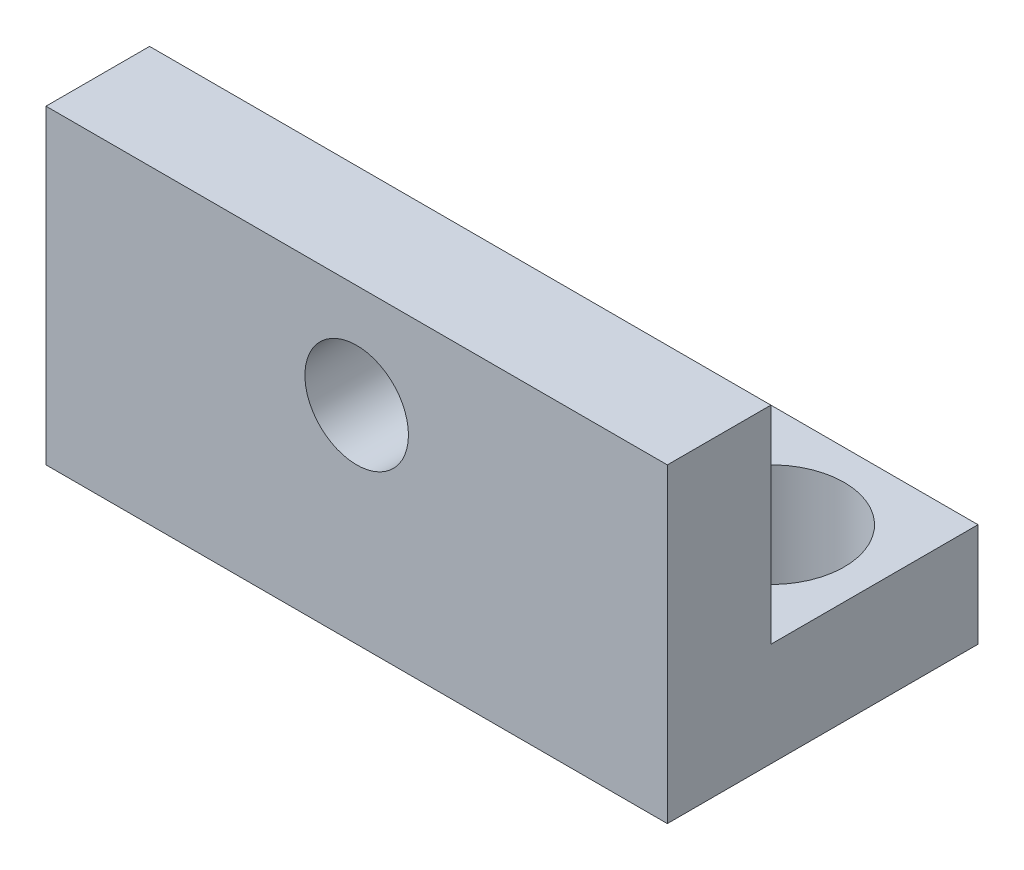
SolidWorks part; units mm, degrees
material "ABS"
ref_plane "Front Plane" through (0, 0, 0) normal (0, 0, 1) x (1, 0, 0)
ref_plane "Top Plane" through (0, 0, 0) normal (0, 1, 0) x (1, 0, 0)
ref_plane "Right Plane" through (0, 0, 0) normal (1, 0, 0) x (0, 0, -1)
sketch "Sketch1" plane through (0, 0, 0) normal (0, 0, 1) x (1, 0, 0)
  line L1 (-9.525, -3.175) -> (9.525, -3.175)
  line L2 (-9.525, -3.175) -> (-9.525, 3.175)
  line L3 (-9.525, 3.175) -> (9.525, 3.175)
  line L4 (9.525, -3.175) -> (9.525, 3.175)
  line L5 (-9.525, -3.175) -> (9.525, 3.175) construction
  line L6 (-9.525, 3.175) -> (9.525, -3.175) construction
  circle A0 centre (0, 0) radius 1.5875
  point P0 (0, 0)
  dimension "D3" = 3.175
  dimension "D1" = 6.35
  dimension "D2" = 19.05
extrude "Boss-Extrude1" add sketch "Sketch1" along normal blind 3.175
sketch "Sketch2" plane through (0, -3.175, 0) normal (0, -1, 0) x (1, 0, 0)
  line L0 (-9.525, 3.175) -> (9.525, 3.175) construction
  line L1 (-9.525, 3.175) -> (9.525, 3.175)
  line L2 (-9.525, 3.175) -> (-9.525, -6.35)
  line L3 (-9.525, -6.35) -> (9.525, -6.35)
  line L4 (9.525, 3.175) -> (9.525, -6.35)
  line L5 (-9.525, 3.175) -> (-9.525, 0) construction
  line L7 (3.4925, 0) -> (-3.4925, 0) construction
  dimension "D1" = 6.35
extrude "Boss-Extrude2" add sketch "Sketch2" along normal blind 3.175
hole_wizard "#8 Clearance Hole1" positions "Sketch3" profile "Sketch4" hole size "#8" standard "ANSI Inch" end condition through all
sketch "Sketch3" plane through (0, -6.35, 0) normal (0, -1, 0) x (-1, 0, 0)
  line L0 (9.525, 3.175) -> (-9.525, 3.175) construction
  line L1 (9.525, 0) -> (9.525, 6.35) construction
  line L2 (-9.525, 6.35) -> (-9.525, 0) construction
  line L4 (0, 6.35) -> (0, -3.175) construction
  line L5 (9.525, 6.35) -> (-9.525, 6.35) construction
  line L6 (-9.525, -3.175) -> (9.525, -3.175) construction
  line L8 (-9.525, 6.35) -> (-9.525, -3.175) construction
  point P9 (6.35, 3.175)
  point P11 (-6.35, 3.175)
  dimension "D1" = 3.175
sketch "Sketch4" plane through (6.35, -6.35, -3.175) normal (1, 0, 0) x (0, 0, -1)
  line L0 (0, 0) -> (0, 9.525)
  line L1 (0, 9.525) -> (2.2479, 9.525)
  line L2 (2.2479, 9.525) -> (2.2479, 0)
  line L5 (2.2479, 0) -> (0, 0)
  line L11 (0, -6.35) -> (0, 107.95) construction
  dimension "Thru Hole Dia." = 4.4958
  dimension "Thru Hole Depth" = 9.525
